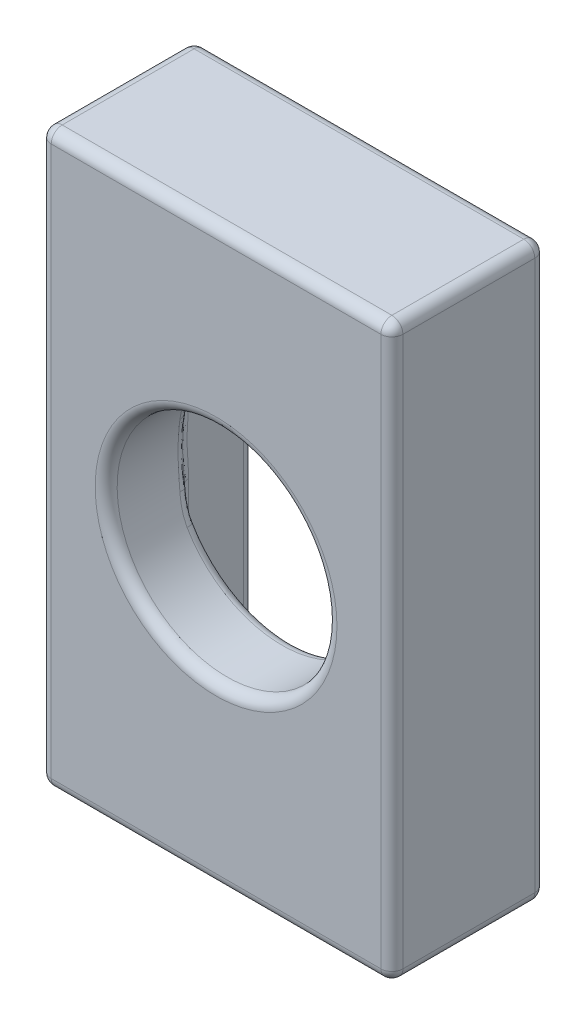
SolidWorks part; units mm, degrees
material "PET"
ref_plane "Front Plane" through (0, 0, 0) normal (0, 0, 1) x (1, 0, 0)
ref_plane "Top Plane" through (0, 0, 0) normal (0, 1, 0) x (1, 0, 0)
ref_plane "Right Plane" through (0, 0, 0) normal (1, 0, 0) x (0, 0, -1)
sketch "Sketch1" plane through (0, 0, 0) normal (0, 0, 1) x (1, 0, 0)
  line L0 (13.25, 23.7906) -> (13.25, 2.2094)
  line L1 (0, 0) -> (16, 0)
  line L2 (0, 0) -> (0, 26)
  line L3 (0, 26) -> (16, 26)
  line L4 (16, 0) -> (16, 26)
  line L5 (2.75, 23.7906) -> (2.75, 2.2094)
  line L6 (2.75, 13) -> (13.25, 13) construction
  arc A0 (2.75, 2.2094) -> (13.25, 2.2094) centre (8, 13) ccw
  arc A1 (13.25, 23.7906) -> (2.75, 23.7906) centre (8, 13) ccw
  point P6 (16, 13)
  point P13 (8, 13)
  point P14 (8, 0)
  dimension "D4" = 24
  dimension "D1" = 26
  dimension "D2" = 16
  dimension "D3" = 10.5
extrude "Boss-Extrude1" add sketch "Sketch1" along normal blind 3.5
sketch "Sketch2" plane through (0, 0, 3.5) normal (0, 0, 1) x (1, 0, 0)
  line L1 (0, 26) -> (16, 26)
  line L2 (0, 26) -> (0, 0)
  line L3 (0, 0) -> (16, 0)
  line L4 (16, 26) -> (16, 0)
extrude "Boss-Extrude2" add sketch "Sketch2" along normal blind 3.5
sketch "Sketch3" plane through (0, 0, 3.5) normal (0, 0, -1) x (-1, 0, 0)
  line L0 (0, 0) -> (-16, 0) construction
  line L1 (-16, 0) -> (-16, 26) construction
  circle A0 centre (-8, 13) radius 5
  point P4 (-8, 0)
  point P7 (-16, 13)
  dimension "D1" = 10
extrude "Cut-Extrude1" cut sketch "Sketch3" against normal through all
fillet "Fillet1" radius 0.5 25 edges at (8, 1, 0) (8, 25, 0) (13.25, 23.7906, 1.75) (13.25, 13, 3.5) (13.25, 2.2094, 1.75) (13.25, 13, 0) (2.75, 2.2094, 1.75) (2.75, 13, 3.5) (2.75, 23.7906, 1.75) (2.75, 13, 0) (8, 0, 0) (8, 26, 0) (16, 0, 3.5) (16, 26, 3.5) (16, 13, 0) (8, 26, 7) (16, 13, 7) (8, 0, 7) (0, 26, 3.5) (0, 13, 7) (0, 0, 3.5) (0, 13, 0) (8, 1, 3.5) (8, 25, 3.5) (3, 13, 7)
fillet "Fillet2" radius 0.5 4 edges at (3, 13, 3.5) (8, 8, 3.5) (13, 13, 3.5) (8, 18, 3.5)
